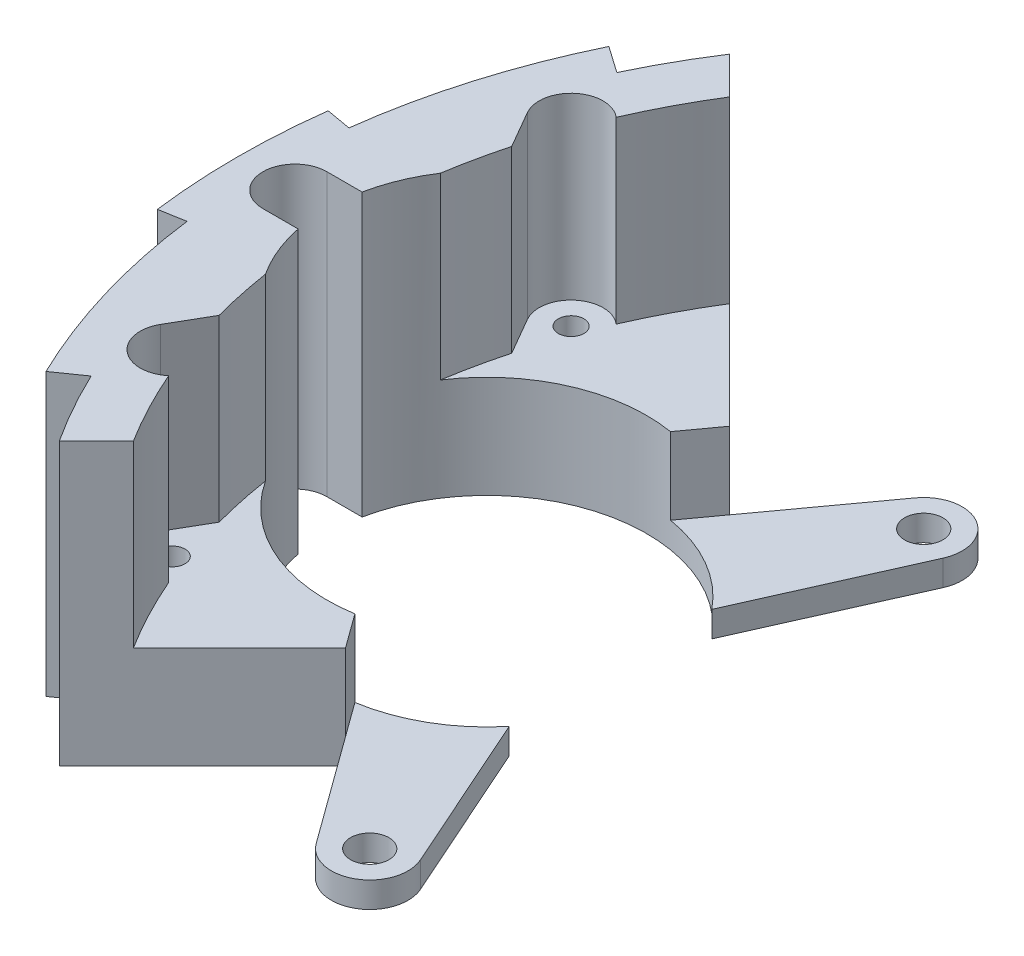
SolidWorks part; units mm, degrees
ref_plane "Front Plane" through (0, 0, 0) normal (0, 0, 1) x (1, 0, 0)
ref_plane "Top Plane" through (0, 0, 0) normal (0, 1, 0) x (1, 0, 0)
ref_plane "Right Plane" through (0, 0, 0) normal (1, 0, 0) x (0, 0, -1)
sketch "Sketch2" plane through (0, 0, 0) normal (0, 1, 0) x (1, 0, 0)
  line L0 (0, 0) -> (-15, 0) construction
  line L1 (-15, 2.5) -> (-12.2474, 2.5)
  line L2 (-15, -2.5) -> (-12.2474, -2.5)
  line L3 (0, 0) -> (33, 0) construction
  line L4 (0, 0) -> (-9, 15.5885) construction
  line L5 (0, 0) -> (12.5, 21.6506) construction
  line L6 (-11.1651, 14.3385) -> (-8.2888, 9.3566)
  line L7 (-6.8349, 16.8385) -> (-3.9587, 11.8566)
  line L8 (10.0729, 23.414) -> (2.0237, 12.3351)
  line L9 (9.6707, -7.9201) -> (15.2406, -20.4304)
  line L10 (9.6707, 7.9201) -> (15.2406, 20.4304)
  line L11 (10.0729, -23.414) -> (2.0237, -12.3351)
  line L12 (-6.8349, -16.8385) -> (-3.9587, -11.8566)
  line L13 (-11.1651, -14.3385) -> (-8.2888, -9.3566)
  line L14 (-12.4569, 21.9982) -> (-10.381, 20.5447)
  line L15 (-12.4569, -21.9982) -> (-10.381, -20.5447)
  line L16 (-10.381, 20.5447) -> (18.9598, 0) construction
  line L17 (-19.0742, 6.673) -> (-17.1021, 6.327)
  line L18 (-19.0742, -6.673) -> (-17.1021, -6.327)
  line L21 (-7.2273, 26.1871) -> (18.9598, 0) construction
  line L22 (-7.2273, 26.1871) -> (3.9598, 15)
  line L23 (-7.2273, -26.1871) -> (3.9598, -15)
  arc A0 (-12.2474, -2.5) -> (-12.2474, 2.5) centre (0, 0) ccw
  arc A2 (-12.4569, 21.9982) -> (-12.4569, -21.9982) centre (33, 0) ccw
  circle A3 centre (33, 0) radius 40 construction
  circle A4 centre (33, 0) radius 27.5 construction
  arc A5 (15.2406, 20.4304) -> (10.0729, 23.414) centre (12.5, 21.6506) ccw
  arc A6 (-6.8349, 16.8385) -> (-11.1651, 14.3385) centre (-9, 15.5885) ccw
  arc A7 (15.2406, -20.4304) -> (10.0729, -23.414) centre (12.5, -21.6506) cw
  arc A8 (-6.8349, -16.8385) -> (-11.1651, -14.3385) centre (-9, -15.5885) cw
  arc A9 (-15, 2.5) -> (-15, -2.5) centre (-15, 0) ccw
  arc A10 (-19.0742, 6.673) -> (-19.0742, -6.673) centre (33, 0) ccw
  circle A11 centre (12.5, 21.6506) radius 1.5
  circle A12 centre (12.5, -21.6506) radius 1.5
  circle A13 centre (-9, 15.5885) radius 1
  circle A14 centre (-9, -15.5885) radius 1
  arc A17 (-10.381, 20.5447) -> (-7.2273, 26.1871) centre (33, 0) cw
  arc A20 (-10.381, -20.5447) -> (-7.2273, -26.1871) centre (33, 0) ccw
  point P11 (-17.5, 0)
  point P14 (-7, 0)
  point P40 (-18.0881, 6.5)
  dimension "D1" = 25
  dimension "D4" = 2.5
  dimension "D6" = 80
  dimension "D7" = 55
  dimension "D8" = 18
  dimension "D12" = 5
  dimension "D13" = 6
  dimension "D18" = 105
  dimension "D20" = 3
  dimension "D21" = 3
  dimension "D22" = 2
  dimension "D26" = 50.5
  dimension "D28" = 48
  dimension "D3" = 15
  dimension "D5" = 7
  dimension "D9" = 25
  dimension "D10" = 60
  dimension "D11" = 120
  dimension "D14" = 6
  dimension "D15" = 6
  dimension "D16" = 35
  dimension "D17" = 15
  dimension "D19" = 4
  dimension "D27" = 45
  dimension "D29" = 33
extrude "Boss-Extrude1" add sketch "Sketch2" along normal blind 8 contours L15 A20 L23 L11 A0 L12 A8 L13 L2 A9 A2 | A8 L12 A0 L13 A14 | A17 L14 A2 A9 L1 A0 L6 A6 L7 L8 L22 | L7 A6 L6 A0 A13 | L17 A10 L18 A2 region at (-17.0072, 0, -2.0072) region at (-18.3715, 0, 0) region at (-17.0072, 0, 2.0072) region at (-8.0238, 0, -13.8976) region at (-8.0238, 0, 13.8976)
extrude "Boss-Extrude9" add sketch "Sketch2<5>" along normal blind 2 contours A7 L9 A0 L11 A12 | L10 A5 L8 A0 A11 region at (9.4405, 0, -16.3513) region at (9.4405, 0, 16.3513)
sketch "Sketch2<5>" plane through (0, 0, 0) normal (0, 1, 0) x (1, 0, 0) same geometry as "Sketch2"
ref_plane "Plane1" through (0, 8, 0) normal (0, 1, 0) x (1, 0, 0)
extrude "Boss-Extrude6" add sketch "Sketch2<4>" along normal blind 2 contours A7 L9 A0 L11 A12 | L10 A5 L8 A0 A11 region at (9.4405, 0, -16.3513) region at (9.4405, 0, 16.3513)
sketch "Sketch2<4>" plane through (0, 0, 0) normal (0, 1, 0) x (1, 0, 0) same geometry as "Sketch2"
sketch "Sketch5" plane through (0, 8, 0) normal (0, 1, 0) x (1, 0, 0)
  line L0 (0, 0) -> (-15, 0) construction
  line L1 (-15, 2.5) -> (-12.2474, 2.5)
  line L2 (-15, -2.5) -> (-12.2474, -2.5)
  line L3 (0, 0) -> (33, 0) construction
  line L4 (0, 0) -> (-9, 15.5885) construction
  line L5 (0, 0) -> (12.5, 21.6506) construction
  line L6 (-11.1651, 14.3385) -> (-8.2888, 9.3566)
  line L7 (-6.8349, 16.8385) -> (-3.9587, 11.8566)
  line L8 (10.0729, 23.414) -> (2.0237, 12.3351)
  line L9 (9.6707, -7.9201) -> (15.2406, -20.4304)
  line L10 (9.6707, 7.9201) -> (15.2406, 20.4304)
  line L11 (10.0729, -23.414) -> (2.0237, -12.3351)
  line L12 (-6.8349, -16.8385) -> (-3.9587, -11.8566)
  line L13 (-11.1651, -14.3385) -> (-8.2888, -9.3566)
  line L14 (-12.4569, 21.9982) -> (-10.381, 20.5447)
  line L15 (-12.4569, -21.9982) -> (-10.381, -20.5447)
  line L16 (-10.381, 20.5447) -> (18.9598, 0) construction
  line L17 (-19.0742, 6.673) -> (-17.1021, 6.327)
  line L18 (-19.0742, -6.673) -> (-17.1021, -6.327)
  line L21 (-7.2273, 26.1871) -> (18.9598, 0) construction
  line L22 (-7.2273, 26.1871) -> (3.9598, 15)
  line L23 (-7.2273, -26.1871) -> (3.9598, -15)
  arc A0 (-12.2474, -2.5) -> (-12.2474, 2.5) centre (0, 0) ccw
  arc A2 (-12.4569, 21.9982) -> (-12.4569, -21.9982) centre (33, 0) ccw
  circle A3 centre (33, 0) radius 40 construction
  circle A4 centre (33, 0) radius 27.5 construction
  arc A5 (15.2406, 20.4304) -> (10.0729, 23.414) centre (12.5, 21.6506) ccw
  arc A6 (-6.8349, 16.8385) -> (-11.1651, 14.3385) centre (-9, 15.5885) ccw
  arc A7 (15.2406, -20.4304) -> (10.0729, -23.414) centre (12.5, -21.6506) cw
  arc A8 (-6.8349, -16.8385) -> (-11.1651, -14.3385) centre (-9, -15.5885) cw
  arc A9 (-15, 2.5) -> (-15, -2.5) centre (-15, 0) ccw
  arc A10 (-19.0742, 6.673) -> (-19.0742, -6.673) centre (33, 0) ccw
  circle A11 centre (12.5, 21.6506) radius 1.5
  circle A12 centre (12.5, -21.6506) radius 1.5
  circle A13 centre (-9, 15.5885) radius 1
  circle A14 centre (-9, -15.5885) radius 1
  arc A17 (-10.381, 20.5447) -> (-7.2273, 26.1871) centre (33, 0) cw
  arc A20 (-10.381, -20.5447) -> (-7.2273, -26.1871) centre (33, 0) ccw
  point P11 (-17.5, 0)
  point P14 (-7, 0)
extrude "Boss-Extrude7" add sketch "Sketch5" along normal blind 14 contours A17 L14 A2 A9 L1 A0 L6 A6 L7 L8 L22 | L15 A20 L23 L11 A0 L12 A8 L13 L2 A9 A2 | L17 A10 L18 A2 region at (-17.0072, 8, -2.0072) region at (-18.3715, 8, 0) region at (-17.0072, 8, 2.0072)
sketch "Sketch7" plane through (0, 22, 0) normal (0, 1, 0) x (1, 0, 0)
  line L0 (0, 0) -> (33, 0) construction
  circle A0 centre (33, 0) radius 44
  dimension "D2" = 88
  dimension "D1" = 33
extrude "Cut-Extrude2" cut sketch "Sketch7" against normal blind 14
ref_axis "TyreCentre" through (33, 0, 0) along (0, 1, 0)
sketch "Sketch9" [suppressed] plane through (0, 0, 0) normal (0, -1, 0) x (1, 0, 0)
  line L0 (-8.2888, 9.3566) -> (-11.1651, 14.3385)
  line L1 (-3.9587, 11.8566) -> (-6.8349, 16.8385)
  line L2 (0, 0) -> (15, 0) construction
  line L3 (-12.3904, 13.0567) -> (0, 0)
  line L4 (0, 0) -> (-5.1123, 17.2588)
  line L5 (-12.5467, 10.7159) -> (0, 0)
  line L6 (0, 0) -> (-3.0069, 16.2237)
  line L7 (-4.6863, 15.8205) -> (-5.4557, 17.1533)
  line L8 (-11.3579, 11.9687) -> (-12.1273, 13.3014)
  circle A0 centre (0, 0) radius 15
  arc A1 (-11.1651, 14.3385) -> (-6.8349, 16.8385) centre (-9, 15.5885) cw
  arc A2 (-6.8349, 16.8385) -> (-11.1651, 14.3385) centre (-9, 15.5885) ccw construction
  arc A3 (-12.3904, 13.0567) -> (-5.1123, 17.2588) centre (0, 0) cw
  arc A4 (-11.3579, 11.9687) -> (-4.6863, 15.8205) centre (0, 0) cw
  arc A5 (-12.5467, 10.7159) -> (-11.3579, 11.9687) centre (0, 0) cw
  arc A6 (-4.6863, 15.8205) -> (-3.0069, 16.2237) centre (0, 0) cw
  point P20 (-9, 15.5885)
  dimension "D1" = 30
  dimension "D2" = 16.5
  dimension "D3" = 27
  dimension "D4" = 6
  dimension "D5" = 6
extrude "Boss-Extrude8" [suppressed] add sketch "Sketch9" along normal blind 2 contours L8 A4 L0 A3 | A4 L3 A0 L0 | A5 L5 A0 L3 | A6 L4 A0 L6 | A4 L1 A0 L4 | L1 A4 L7 A3
mirror "Mirror3" [suppressed] about plane through (0, 0, 0) normal (0, 0, 1)
